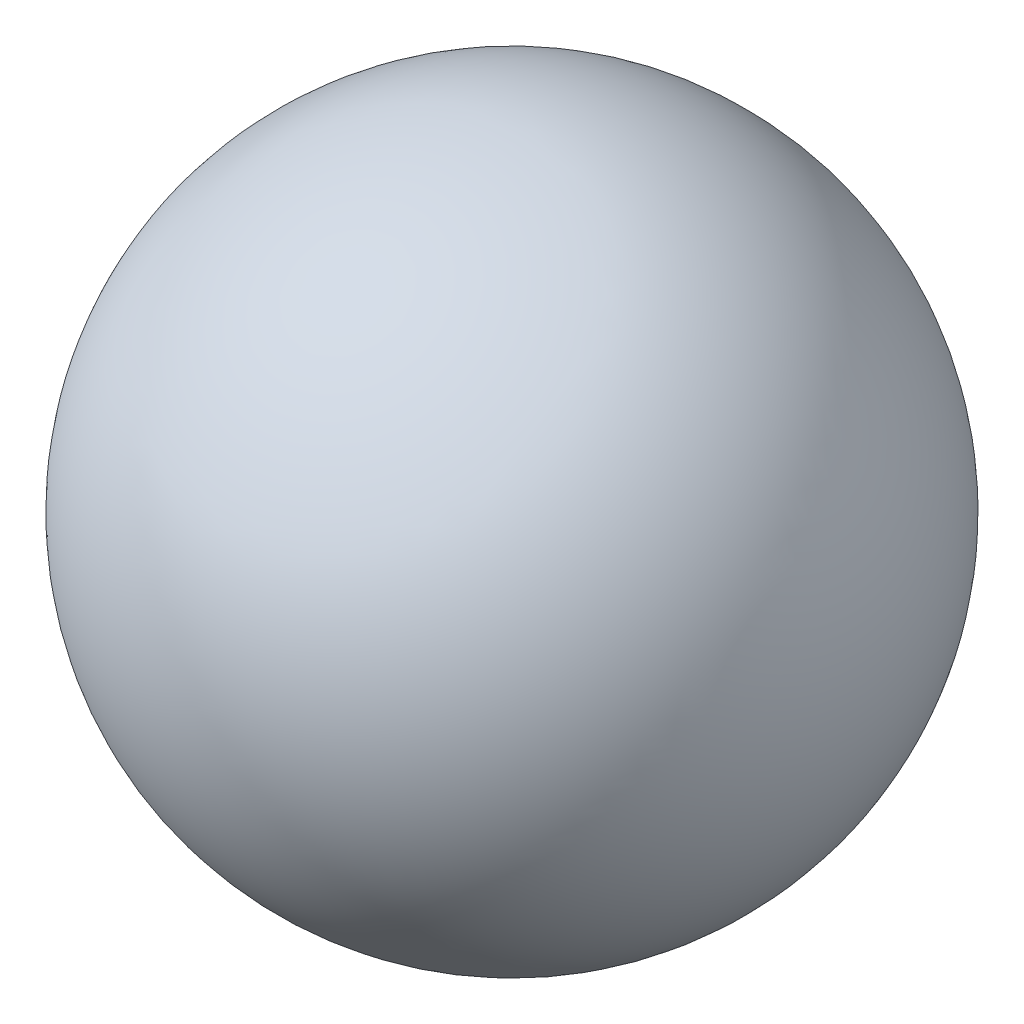
SolidWorks part; units mm, degrees
ref_plane "Plan de face" through (0, 0, 0) normal (0, 0, 1) x (1, 0, 0)
ref_plane "Plan de dessus" through (0, 0, 0) normal (0, 1, 0) x (1, 0, 0)
ref_plane "Plan de droite" through (0, 0, 0) normal (1, 0, 0) x (0, 0, -1)
sketch "Esquisse1" plane through (0, 0, 0) normal (0, 0, 1) x (1, 0, 0)
  line L0 (-40, 0) -> (40, 0)
  arc A0 (-40, 0) -> (40, 0) centre (0, 0) ccw
  point P4 (0, 0)
  dimension "D1" = 40
  dimension "D2" = 80
revolve "Révolution1" add sketch "Esquisse1" angle 360 about L0
